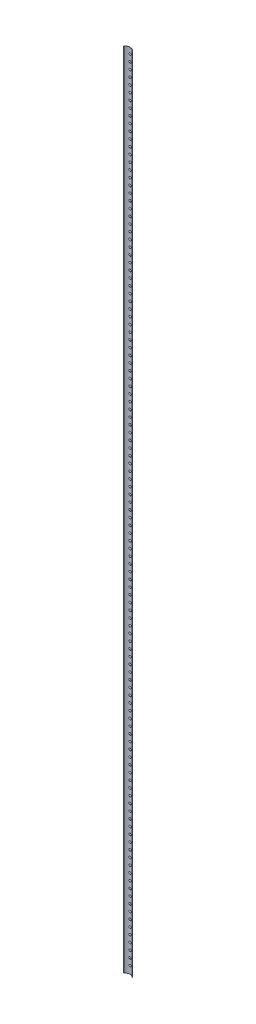
SolidWorks part; units mm, degrees
ref_plane "Front Plane" through (0, 0, 0) normal (0, 0, 1) x (1, 0, 0)
ref_plane "Top Plane" through (0, 0, 0) normal (0, 1, 0) x (1, 0, 0)
ref_plane "Right Plane" through (0, 0, 0) normal (1, 0, 0) x (0, 0, -1)
sketch "Sketch2" plane through (0, 0, 0) normal (0, 1, 0) x (1, 0, 0)
  line L2 (-18.3917, -0.1313) -> (-18.0217, -0.1313)
  line L3 (10.0773, -0.1313) -> (10.4983, -0.1313)
  arc A0 (-18.3917, -0.1313) -> (10.4983, -0.1313) centre (-3.9467, -9.5626) cw
  arc A1 (-18.0217, -0.1313) -> (10.0773, -0.1313) centre (-3.9722, -9.5455) cw
  dimension "D2" = 28.89
  dimension "D3" = 0.37
  dimension "D1" = 0.37
extrude "Boss-Extrude1" add sketch "Sketch2" along normal blind 2743.2
ref_plane "Plane1" through (-18.3917, 0, 0.1313) normal (0, -1, 0) x (-1, 0, 0)
sketch "Sketch4" plane through (0, 0, 0.1313) normal (0, 0, 1) x (1, 0, 0)
  circle A1 centre (-3.9467, 25.4) radius 3.81
  point P0 (0, 0)
  dimension "D2" = 7.62
extrude "Cut-Extrude2" cut sketch "Sketch4" against normal blind 25.4
pattern_linear "LPattern1" count 120 spacing 22.86 along (0, 1, 0) of "Cut-Extrude2"
